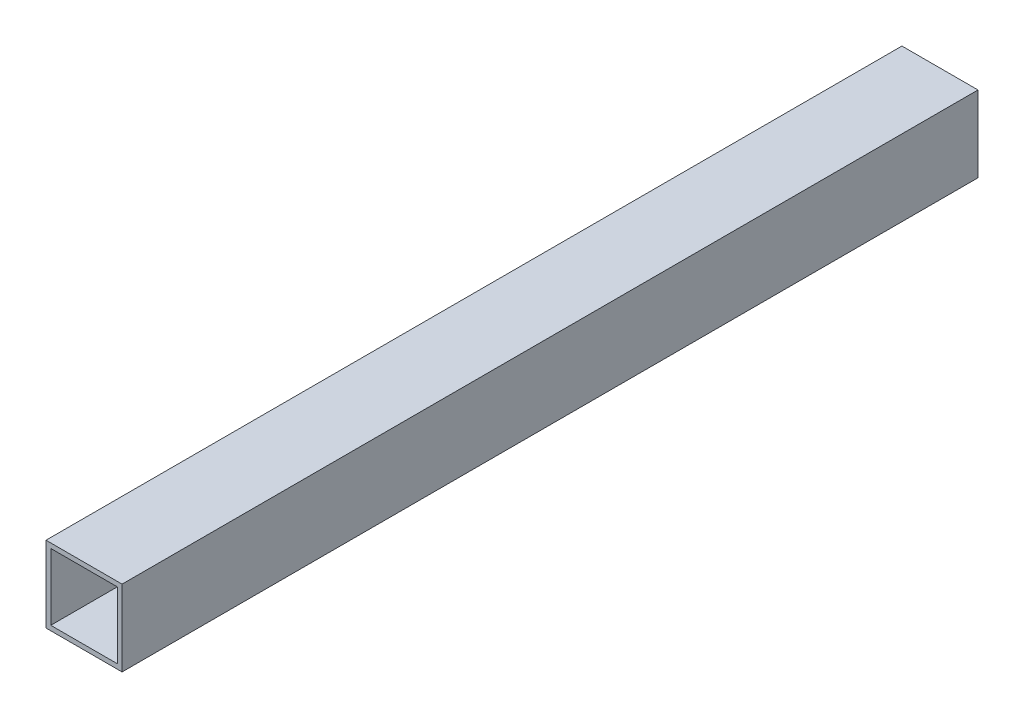
SolidWorks part; units mm, degrees
material "6061-T6 (SS)"
ref_plane "Front" through (0, 0, 0) normal (0, 0, 1) x (1, 0, 0)
ref_plane "Top" through (0, 0, 0) normal (0, 1, 0) x (1, 0, 0)
ref_plane "Right" through (0, 0, 0) normal (1, 0, 0) x (0, 0, -1)
sketch "Sketch1" plane through (0, 0, 0) normal (0, 0, 1) x (1, 0, 0)
  line L0 (-17.5, -17.5) -> (-17.5, 17.5)
  line L1 (-20, -20) -> (20, -20)
  line L2 (-20, -20) -> (-20, 20)
  line L3 (-20, 20) -> (20, 20)
  line L4 (20, -20) -> (20, 20)
  line L5 (-20, -20) -> (20, 20) construction
  line L6 (-20, 20) -> (20, -20) construction
  line L7 (-17.5, 17.5) -> (17.5, 17.5)
  line L8 (17.5, -17.5) -> (17.5, 17.5)
  line L9 (-17.5, -17.5) -> (17.5, -17.5)
  point P0 (0, 0)
  dimension "D2" = 40
  dimension "D1" = 2.5
extrude "Boss-Extrude1" add sketch "Sketch1" along normal mid plane 450
